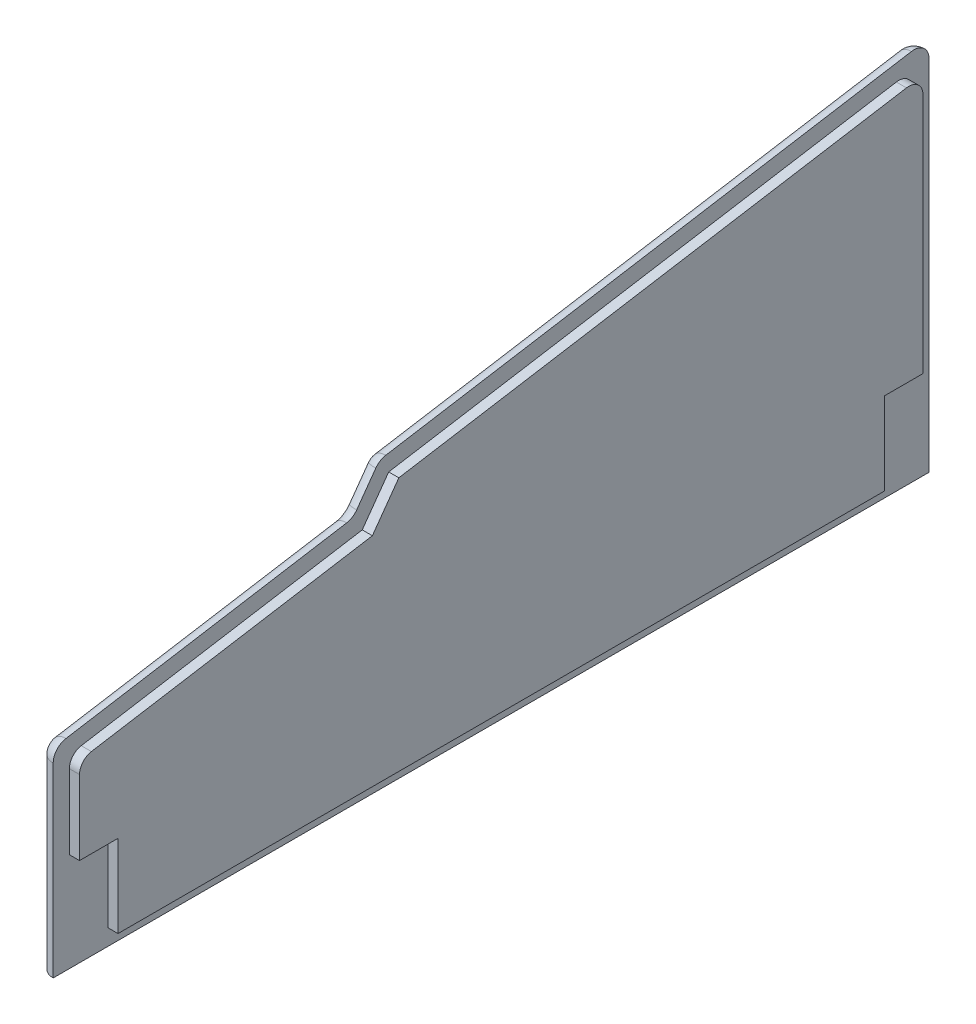
SolidWorks part; units mm, degrees
ref_plane "Front Plane" through (0, 0, 0) normal (0, 0, 1) x (1, 0, 0)
ref_plane "Top Plane" through (0, 0, 0) normal (0, 1, 0) x (1, 0, 0)
ref_plane "Right Plane" through (0, 0, 0) normal (1, 0, 0) x (0, 0, -1)
sketch "Sketch1" plane through (-329.9746, 0, 0) normal (-1, 0, 0) x (0, 0, 1)
  line L0 (-32.649, -10.2195) -> (-32.649, -19.5021)
  line L1 (-32.649, -19.5021) -> (140.305, -19.5021)
  line L2 (140.305, -19.5021) -> (140.305, -10.2195)
  line L3 (-26.049, -0.2195) -> (-22.049, -0.2195) construction
  line L4 (-22.049, -0.2195) -> (-22.049, -16.5021) construction
  line L5 (-22.049, -16.5021) -> (129.705, -16.5021) construction
  line L6 (129.705, -16.5021) -> (129.705, -0.2195) construction
  line L7 (129.705, -0.2195) -> (133.705, -0.2195) construction
  line L8 (-29.649, -0.2195) -> (-32.649, -0.2195) construction
  line L9 (32.683, -16.5021) -> (32.683, -19.5021) construction
  line L10 (-29.449, -0.0195) -> (-29.449, 47.7081)
  line L11 (-26.1927, 50.4707) -> (74.0512, 33.9125)
  line L12 (74.0512, 33.9125) -> (79.2779, 26.6175)
  line L13 (79.2779, 26.6175) -> (134.7613, 17.4528)
  line L14 (137.105, 14.6903) -> (137.105, -0.0195)
  line L15 (137.105, -0.0195) -> (133.705, -0.0195)
  line L16 (74.6544, 37.0563) -> (-29.1601, 54.2042)
  line L17 (-32.649, 51.2443) -> (-32.649, -10.2195)
  line L18 (-32.649, -10.2195) -> (-26.049, -10.2195)
  line L19 (-26.049, -10.2195) -> (-26.049, -0.2195)
  line L20 (-26.049, -0.2195) -> (-29.649, -0.2195)
  line L21 (-29.649, -0.2195) -> (-29.649, 47.7081)
  line L22 (-26.1601, 50.668) -> (74.1655, 34.0964)
  line L23 (74.1655, 34.0964) -> (79.3922, 26.8013)
  line L24 (79.3922, 26.8013) -> (134.7939, 17.6502)
  line L25 (137.305, 14.6903) -> (137.305, -0.2195)
  line L26 (137.305, -0.2195) -> (133.705, -0.2195)
  line L27 (133.705, -0.2195) -> (133.705, -10.2195)
  line L28 (133.705, -10.2195) -> (140.305, -10.2195)
  line L29 (140.305, -10.2195) -> (140.305, 17.2354)
  line L30 (137.7939, 20.1953) -> (82.3332, 29.3562)
  line L31 (80.3834, 30.5688) -> (76.6042, 35.8436)
  line L32 (74.6544, 37.0563) -> (-29.1601, 54.2042)
  line L33 (-32.649, 51.2443) -> (-32.649, -10.2195)
  line L35 (-26.049, -10.2195) -> (-26.049, -0.2195) construction
  line L36 (-26.049, -0.2195) -> (-29.649, -0.2195) construction
  line L37 (-29.649, -0.2195) -> (-29.649, 47.7081) construction
  line L38 (-26.1601, 50.668) -> (74.1655, 34.0964) construction
  line L39 (74.1655, 34.0964) -> (79.3922, 26.8013) construction
  line L40 (79.3922, 26.8013) -> (134.7939, 17.6502) construction
  line L41 (137.305, 14.6903) -> (137.305, -0.2195) construction
  line L42 (137.305, -0.2195) -> (133.705, -0.2195) construction
  line L43 (133.705, -0.2195) -> (133.705, -10.2195) construction
  line L45 (140.305, -10.2195) -> (140.305, 17.2354)
  line L46 (137.7939, 20.1953) -> (82.3332, 29.3562)
  line L47 (80.3834, 30.5688) -> (76.6042, 35.8436)
  line L48 (129.505, -0.0195) -> (133.705, -0.0195)
  line L49 (129.505, -16.3021) -> (129.505, -0.0195)
  line L50 (-21.849, -16.3021) -> (129.505, -16.3021)
  line L51 (-21.849, -0.0195) -> (-21.849, -16.3021)
  line L52 (-26.049, -0.0195) -> (-21.849, -0.0195)
  line L53 (-26.049, -0.0195) -> (-29.449, -0.0195)
  arc A0 (-26.1927, 50.4707) -> (-29.449, 47.7081) centre (-26.649, 47.7081) ccw
  arc A1 (137.105, 14.6903) -> (134.7613, 17.4528) centre (134.305, 14.6903) ccw
  arc A6 (-29.1601, 54.2042) -> (-32.649, 51.2443) centre (-29.649, 51.2443) ccw
  arc A7 (-26.1601, 50.668) -> (-29.649, 47.7081) centre (-26.649, 47.7081) ccw
  arc A8 (137.305, 14.6903) -> (134.7939, 17.6502) centre (134.305, 14.6903) ccw
  arc A9 (140.305, 17.2354) -> (137.7939, 20.1953) centre (137.305, 17.2354) ccw
  arc A10 (80.3834, 30.5688) -> (82.3332, 29.3562) centre (82.8221, 32.3161) ccw
  arc A11 (76.6042, 35.8436) -> (74.6544, 37.0563) centre (74.1655, 34.0964) ccw
  arc A12 (-29.1601, 54.2042) -> (-32.649, 51.2443) centre (-29.649, 51.2443) ccw
  arc A13 (-26.1601, 50.668) -> (-29.649, 47.7081) centre (-26.649, 47.7081) ccw construction
  arc A14 (137.305, 14.6903) -> (134.7939, 17.6502) centre (134.305, 14.6903) ccw construction
  arc A15 (140.305, 17.2354) -> (137.7939, 20.1953) centre (137.305, 17.2354) ccw
  arc A16 (80.3834, 30.5688) -> (82.3332, 29.3562) centre (82.8221, 32.3161) ccw
  arc A17 (76.6042, 35.8436) -> (74.6544, 37.0563) centre (74.1655, 34.0964) ccw
  line M23 (74.6544, 37.0563) -> (-29.1601, 54.2042)
  arc M24 (-29.1601, 54.2042) -> (-32.649, 51.2443) centre (-29.649, 51.2443) ccw
  line M25 (-32.649, 51.2443) -> (-32.649, -10.2195)
  line M26 (-32.649, -10.2195) -> (-26.049, -10.2195)
  line M27 (-26.049, -10.2195) -> (-26.049, -0.2195)
  line M28 (-26.049, -0.2195) -> (-29.649, -0.2195)
  line M29 (-29.649, -0.2195) -> (-29.649, 47.7081)
  arc M30 (-29.649, 47.7081) -> (-26.1601, 50.668) centre (-26.649, 47.7081) cw
  line M31 (-26.1601, 50.668) -> (74.1655, 34.0964)
  line M32 (74.1655, 34.0964) -> (79.3922, 26.8013)
  line M33 (79.3922, 26.8013) -> (134.7939, 17.6502)
  arc M34 (134.7939, 17.6502) -> (137.305, 14.6903) centre (134.305, 14.6903) cw
  line M35 (137.305, 14.6903) -> (137.305, -0.2195)
  line M36 (137.305, -0.2195) -> (133.705, -0.2195)
  line M37 (133.705, -0.2195) -> (133.705, -10.2195)
  line M38 (133.705, -10.2195) -> (140.305, -10.2195)
  line M39 (140.305, -10.2195) -> (140.305, 17.2354)
  arc M40 (140.305, 17.2354) -> (137.7939, 20.1953) centre (137.305, 17.2354) ccw
  line M41 (137.7939, 20.1953) -> (82.3332, 29.3562)
  arc M42 (82.3332, 29.3562) -> (80.3834, 30.5688) centre (82.8221, 32.3161) cw
  line M43 (80.3834, 30.5688) -> (76.6042, 35.8436)
  arc M44 (76.6042, 35.8436) -> (74.6544, 37.0563) centre (74.1655, 34.0964) ccw
  dimension "D2" = 4
  dimension "D1" = 0
  dimension "D3" = 0.2
extrude "Boss-Extrude1" add sketch "Sketch1" against normal blind 2 contours L14 A1 L13 L12 L11 A0 L10 L53 L52 L51 L50 L49 L48 L15 region at (-329.9746, 10.9572, 43.6701)
extrude "Boss-Extrude2" add sketch "Sketch1<4>" along normal blind 3 contours L1 L2 L0 A1 L14 L15 L48 L49 L50 L51 L52 L53 L10 A0 L11 L12 L13 M38 M37 M36 M35 M34 M33 M32 M31 M30 M29 M28 M27 M26 | M44 M23 M24 M25 M26 M27 M28 M29 M30 M31 M32 M33 M34 M35 M36 M37 M38 M39 M40 M41 M42 M43 | L14 A1 L13 L12 L11 A0 L10 L53 L52 L51 L50 L49 L48 L15 region at (-329.9746, -12.0861, -29.349) region at (-329.9746, 20.5124, -30.8032) region at (-329.9746, 10.9572, 43.6701)
sketch "Sketch1<4>" plane through (-329.9746, 0, 0) normal (-1, 0, 0) x (0, 0, 1) same geometry as "Sketch1"
fillet "Fillet1" radius 3 9 edges at (-332.9746, 15.8711, -32.649) (-332.9746, 53.532, -31.5898) (-332.9746, 45.6302, 22.7472) (-332.9746, 36.6439, 75.7499) (-332.9746, 33.2062, 78.4938) (-332.9746, 29.7686, 81.2377) (-332.9746, 24.7757, 110.0635) (-332.9746, 19.1762, 139.5927) (-332.9746, -1.1334, 140.305)
mirror "Mirror1" about plane through (-327.9746, 0, 0) normal (-1, 0, 0) of bodies 102
delete or keep bodies "Body-Delete/Keep 1" type keep bodies bodies 102
